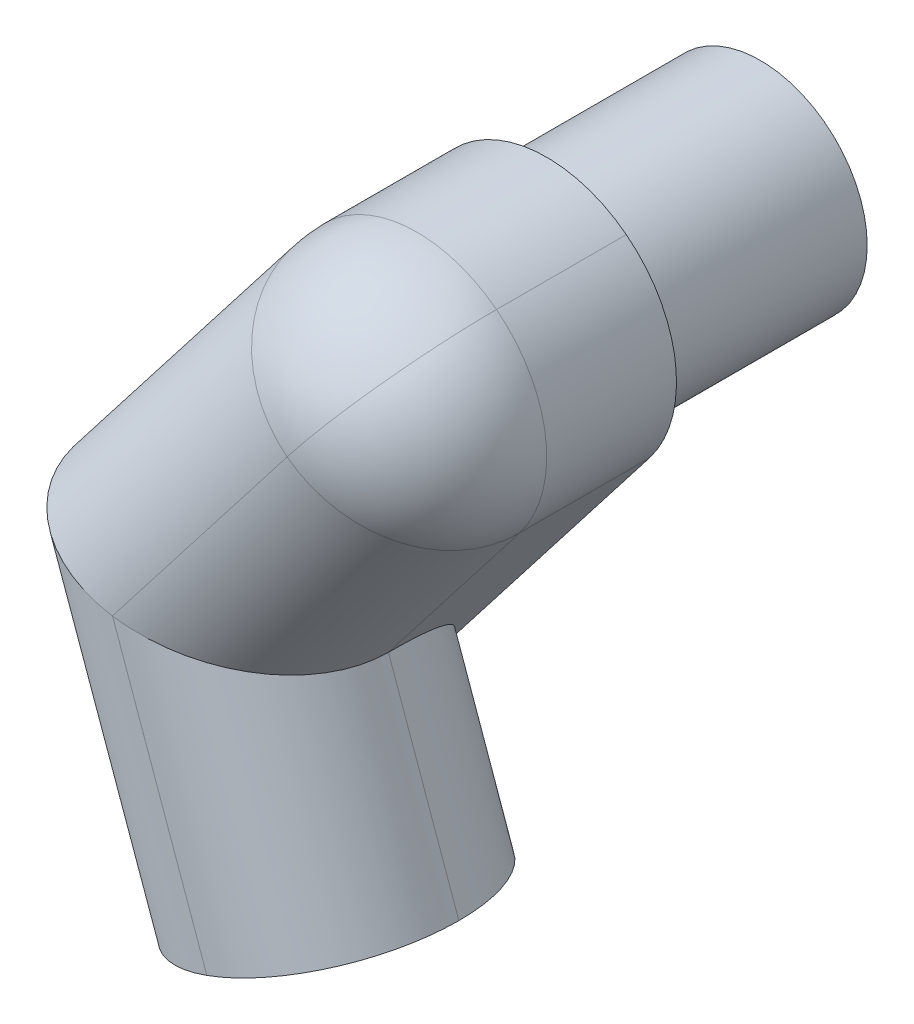
SolidWorks part; units mm, degrees
ref_plane "Front Plane" through (0, 0, 0) normal (0, 0, 1) x (1, 0, 0)
ref_plane "Top Plane" through (0, 0, 0) normal (0, 1, 0) x (1, 0, 0)
ref_plane "Right Plane" through (0, 0, 0) normal (1, 0, 0) x (0, 0, -1)
sketch "Sketch1" plane through (0, 0, 0) normal (0, 0, 1) x (1, 0, 0)
  line L1 (38.8847, 109.2543) -> (-61.2604, -19.7614) construction
  line L2 (-61.2604, -19.7614) -> (-27.772, -113.5288) construction
  line L4 (-61.2604, -19.7614) -> (38.8847, 109.2543)
  line L6 (38.8847, 109.2543) -> (-58.6295, 184.9471)
  line L7 (-58.6295, 184.9471) -> (-200.2781, 2.4629)
  line L8 (-61.2604, -19.7614) -> (-27.772, -113.5288)
  line L9 (-27.772, -113.5288) -> (-144.0244, -155.0475)
  line L10 (-144.0244, -155.0475) -> (-200.2781, 2.4629)
  dimension "D1" = 99.568
  dimension "D2" = 123.444
  dimension "D3" = 123.444
  dimension "D4" = 163.322
extrude "Boss-Extrude1" add sketch "Sketch1" along normal blind 123.444
fillet "Fillet1" radius 61.722 6 edges at (-44.5162, -66.6451, 123.444) (-172.1513, -76.2923, 123.444) (-172.1513, -76.2923, 0) (-44.5162, -66.6451, 0) (-11.1879, 44.7464, 123.444) (-129.4538, 93.705, 123.444)
fillet "Fillet2" radius 61.722 4 edges at (-58.6295, 184.9471, 30.861) (38.8847, 109.2543, 30.861) (24.604, 120.3392, 105.366) (-44.3489, 173.8621, 105.366)
sketch "Sketch3" plane through (0, 0, 0) normal (0, 0, -1) x (-1, 0, 0)
  line L0 (106.1478, -77.5893) -> (-1.0383, 60.4972) construction
  circle A1 centre (47.7188, 98.3436) radius 50.8
  dimension "D1" = 101.6
  dimension "D2" = 61.722
  dimension "D3" = 61.722
extrude "Boss-Extrude2" add sketch "Sketch3" along normal blind 101.6
sketch "Sketch4" plane through (32.8177, -91.8896, 0) normal (0.3363, -0.9417, 0) x (0.9417, 0.3363, 0)
  circle A0 centre (-126.0599, 61.722) radius 50.8
  dimension "D1" = 101.6
  dimension "D2" = 61.722
  dimension "D3" = 61.722
extrude "Cut-Extrude1" cut sketch "Sketch4" against normal blind 101.6
